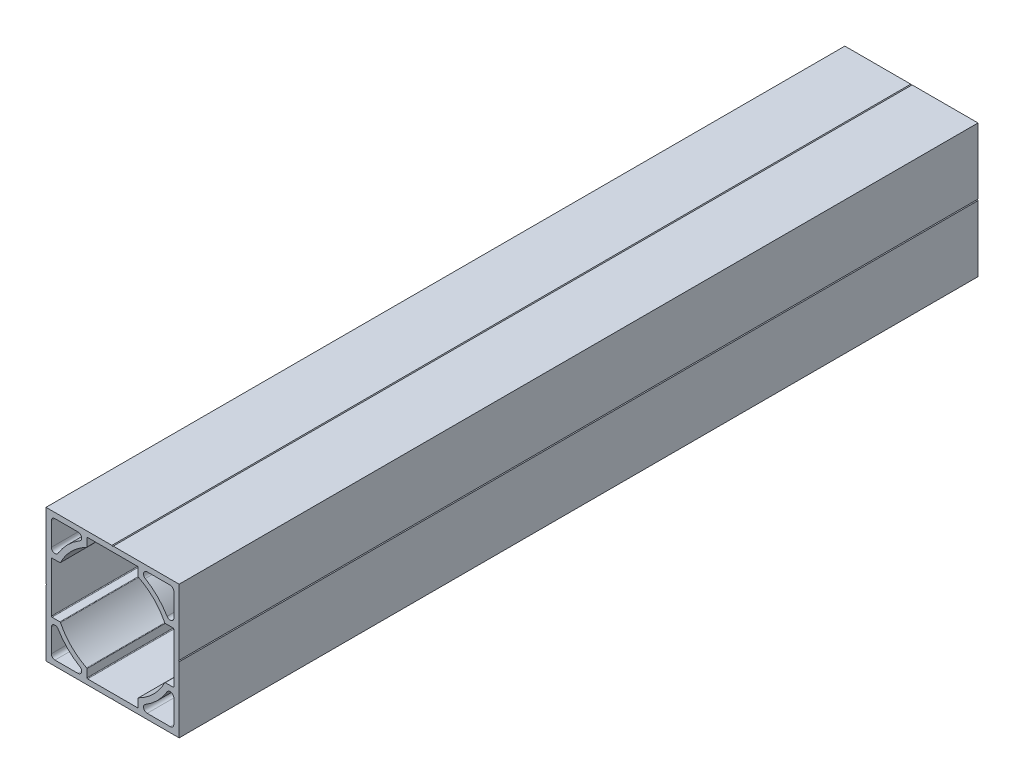
SolidWorks part; units mm, degrees
material "6061 Alloy"
ref_plane "Front Plane" through (0, 0, 0) normal (0, 0, 1) x (1, 0, 0)
ref_plane "Top Plane" through (0, 0, 0) normal (0, 1, 0) x (1, 0, 0)
ref_plane "Right Plane" through (0, 0, 0) normal (1, 0, 0) x (0, 0, -1)
other "Configuration Table"
sketch "Sketch1" plane through (0, 0, 0) normal (0, 0, 1) x (1, 0, 0)
  line L6 (1.7076, 1.016) -> (6.1029, 1.016)
  line L7 (1.016, 6.1029) -> (1.016, 1.7076)
  line L10 (25.4, 12.827) -> (25.4, 25.4)
  line L11 (25.4, 25.4) -> (12.827, 25.4)
  line L14 (12.573, 25.4) -> (0, 25.4)
  line L15 (0, 25.4) -> (0, 12.827)
  line L16 (0, 12.827) -> (0.127, 12.7)
  line L17 (0.127, 12.7) -> (0, 12.573)
  line L18 (0, 12.573) -> (0, 0)
  line L22 (12.827, 0) -> (25.4, 0)
  line L23 (25.4, 0) -> (25.4, 12.573)
  line L24 (1.143, 7.8105) -> (2.6421, 7.8105)
  line L25 (1.016, 17.4625) -> (1.016, 7.9375)
  line L26 (2.6421, 17.5895) -> (1.143, 17.5895)
  line L27 (1.016, 23.6924) -> (1.016, 19.2971)
  line L28 (6.1029, 24.384) -> (1.7076, 24.384)
  line L29 (17.5895, 22.7579) -> (17.5895, 24.257)
  line L30 (17.4625, 24.384) -> (7.9375, 24.384)
  line L31 (7.8105, 24.257) -> (7.8105, 22.7579)
  line L32 (23.6924, 24.384) -> (19.2971, 24.384)
  line L33 (24.384, 19.2971) -> (24.384, 23.6924)
  line L34 (22.7579, 7.8105) -> (24.257, 7.8105)
  line L35 (24.384, 7.9375) -> (24.384, 17.4625)
  line L36 (24.257, 17.5895) -> (22.7579, 17.5895)
  line L37 (24.384, 1.7076) -> (24.384, 6.1029)
  line L38 (19.2971, 1.016) -> (23.6924, 1.016)
  line L39 (7.8105, 2.6421) -> (7.8105, 1.143)
  line L40 (7.9375, 1.016) -> (17.4625, 1.016)
  line L41 (17.5895, 1.143) -> (17.5895, 2.6421)
  line L44 (12.827, 25.4) -> (12.7, 25.273)
  line L45 (12.7, 25.273) -> (12.573, 25.4)
  line L46 (25.4, 12.573) -> (25.273, 12.7)
  line L47 (25.273, 12.7) -> (25.4, 12.827)
  line L48 (12.573, 0) -> (12.7, 0.127)
  line L49 (12.7, 0.127) -> (12.827, 0)
  line L50 (12.573, 0) -> (0, 0)
  arc A14 (1.016, 1.7076) -> (1.7076, 1.016) centre (1.7076, 1.7076) ccw
  arc A15 (2.3006, 6.4588) -> (1.016, 6.1029) centre (1.7076, 6.1029) ccw
  arc A16 (2.3006, 6.4588) -> (6.4588, 2.3006) centre (12.7, 12.7) ccw
  arc A17 (6.1029, 1.016) -> (6.4588, 2.3006) centre (6.1029, 1.7076) ccw
  arc A18 (2.7558, 7.7402) -> (7.7402, 2.7558) centre (12.7, 12.7) ccw
  arc A19 (2.7558, 7.7402) -> (2.6421, 7.8105) centre (2.6421, 7.6835) ccw
  arc A20 (1.016, 7.9375) -> (1.143, 7.8105) centre (1.143, 7.9375) ccw
  arc A21 (1.143, 17.5895) -> (1.016, 17.4625) centre (1.143, 17.4625) ccw
  arc A22 (2.6421, 17.5895) -> (2.7558, 17.6598) centre (2.6421, 17.7165) ccw
  arc A23 (1.016, 19.2971) -> (2.3006, 18.9412) centre (1.7076, 19.2971) ccw
  arc A24 (6.4588, 23.0994) -> (2.3006, 18.9412) centre (12.7, 12.7) ccw
  arc A25 (6.4588, 23.0994) -> (6.1029, 24.384) centre (6.1029, 23.6924) ccw
  arc A26 (1.7076, 24.384) -> (1.016, 23.6924) centre (1.7076, 23.6924) ccw
  arc A27 (17.5895, 24.257) -> (17.4625, 24.384) centre (17.4625, 24.257) ccw
  arc A28 (17.5895, 22.7579) -> (17.6598, 22.6442) centre (17.7165, 22.7579) ccw
  arc A29 (7.9375, 24.384) -> (7.8105, 24.257) centre (7.9375, 24.257) ccw
  arc A30 (7.7402, 22.6442) -> (7.8105, 22.7579) centre (7.6835, 22.7579) ccw
  arc A31 (7.7402, 22.6442) -> (2.7558, 17.6598) centre (12.7, 12.7) ccw
  arc A32 (19.2971, 24.384) -> (18.9412, 23.0994) centre (19.2971, 23.6924) ccw
  arc A33 (23.0994, 18.9412) -> (18.9412, 23.0994) centre (12.7, 12.7) ccw
  arc A34 (23.0994, 18.9412) -> (24.384, 19.2971) centre (23.6924, 19.2971) ccw
  arc A35 (24.384, 23.6924) -> (23.6924, 24.384) centre (23.6924, 23.6924) ccw
  arc A36 (24.257, 7.8105) -> (24.384, 7.9375) centre (24.257, 7.9375) ccw
  arc A37 (22.7579, 7.8105) -> (22.6442, 7.7402) centre (22.7579, 7.6835) ccw
  arc A38 (24.384, 17.4625) -> (24.257, 17.5895) centre (24.257, 17.4625) ccw
  arc A39 (22.6442, 17.6598) -> (22.7579, 17.5895) centre (22.7579, 17.7165) ccw
  arc A40 (22.6442, 17.6598) -> (17.6598, 22.6442) centre (12.7, 12.7) ccw
  arc A41 (24.384, 6.1029) -> (23.0994, 6.4588) centre (23.6924, 6.1029) ccw
  arc A42 (18.9412, 2.3006) -> (23.0994, 6.4588) centre (12.7, 12.7) ccw
  arc A43 (18.9412, 2.3006) -> (19.2971, 1.016) centre (19.2971, 1.7076) ccw
  arc A44 (23.6924, 1.016) -> (24.384, 1.7076) centre (23.6924, 1.7076) ccw
  arc A45 (7.8105, 1.143) -> (7.9375, 1.016) centre (7.9375, 1.143) ccw
  arc A46 (7.8105, 2.6421) -> (7.7402, 2.7558) centre (7.6835, 2.6421) ccw
  arc A47 (17.4625, 1.016) -> (17.5895, 1.143) centre (17.4625, 1.143) ccw
  arc A48 (17.6598, 2.7558) -> (17.5895, 2.6421) centre (17.7165, 2.6421) ccw
  arc A49 (17.6598, 2.7558) -> (22.6442, 7.7402) centre (12.7, 12.7) ccw
  point P41 (12.7, 24.384)
  point P109 (12.7, 12.7)
  point P116 (12.7, 12.7)
  dimension "D1" = 25.4
  dimension "D2" = 1.016
  dimension "D3" = 4
  dimension "D4" = 1.016
  dimension "D7" = 0.127
  dimension "D12" = 11.1125
  dimension "D5" = 0.127
  dimension "D13" = 12.1285
  dimension "D6" = 9.525
  dimension "D8" = 135
  dimension "D9" = 5.7785
  dimension "D10" = 0.127
  dimension "D11" = 4
extrude "Boss-Extrude1" add sketch "Sketch1" along normal blind 152.4
sketch "Sketch2" [suppressed] plane through (0, 0, 0) normal (-1, 0, 0) x (0, 0, 1)
  line L0 (82.55, 12.7) -> (0, 12.7) construction
  line L1 (0, 12.573) -> (0, 0) construction
  circle A0 centre (12.7, 12.7) radius 2.54
  dimension "D1" = 5.08
  dimension "D2" = 12.7
extrude "Cut-Extrude1" [suppressed] cut sketch "Sketch2" against normal through all
pattern_circular "CirPattern1" [suppressed] count 4 over 360 reverse direction yes of bodies 102
pattern_linear "LPattern1" [suppressed] count 95 spacing 12.7 of bodies 103
equation "\"Length\"= 6"
equation "\"D1@Boss-Extrude1\"=\"Length\""
